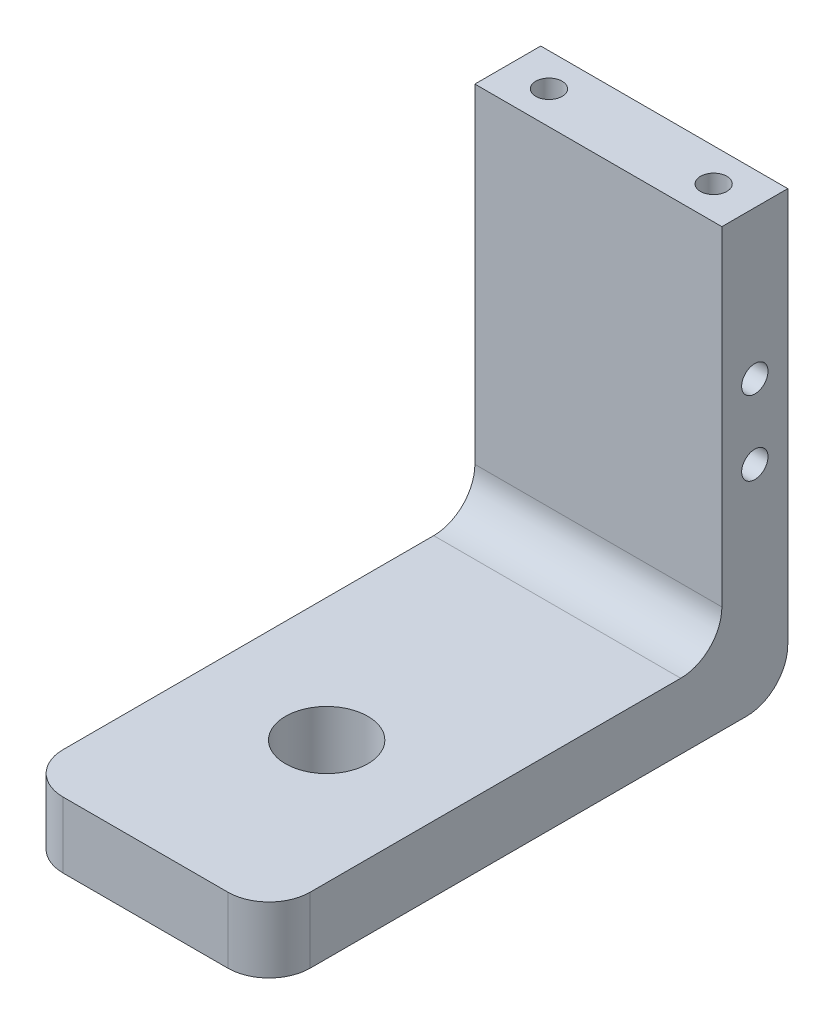
SolidWorks part; units mm, degrees
ref_plane "Front Plane" through (0, 0, 0) normal (0, 0, 1) x (1, 0, 0)
ref_plane "Top Plane" through (0, 0, 0) normal (0, 1, 0) x (1, 0, 0)
ref_plane "Right Plane" through (0, 0, 0) normal (1, 0, 0) x (0, 0, -1)
sketch "Sketch1" plane through (0, 0, 0) normal (1, 0, 0) x (0, 0, -1)
  line L1 (0, 0) -> (63, 0)
  line L2 (0, 0) -> (0, 8)
  line L3 (0, 8) -> (63, 8)
  line L4 (63, 0) -> (63, 8)
  dimension "D1" = 8
  dimension "D2" = 63
extrude "Boss-Extrude1" add sketch "Sketch1" along normal blind 30 contours L3 L4 L1 L2
sketch "Sketch2" plane through (0, 8, 0) normal (0, 1, 0) x (1, 0, 0)
  line L0 (30, 0) -> (30, 63) construction
  line L1 (0, 63) -> (30, 63)
  line L2 (0, 63) -> (0, 55)
  line L3 (0, 55) -> (30, 55)
  line L4 (30, 63) -> (30, 55)
  dimension "D1" = 8
extrude "Boss-Extrude2" add sketch "Sketch2" along normal blind 45
sketch "Sketch3" plane through (0, 8, 0) normal (0, 1, 0) x (1, 0, 0)
  line L0 (30, 0) -> (0, 0) construction
  circle A0 centre (15, 22) radius 5
  point P4 (15, 0)
  point P5 (0, 0)
  dimension "D2" = 10
  dimension "D1" = 22
extrude "Cut-Extrude1" cut sketch "Sketch3" against normal through all
sketch "Sketch4" plane through (30, 0, 0) normal (1, 0, 0) x (0, 0, -1)
  line L0 (0, 0) -> (63, 0) construction
  line L1 (55, 53) -> (63, 53) construction
  circle A0 centre (59, 35) radius 1.6
  circle A1 centre (59, 26) radius 1.6
  point P4 (0, 0)
  point P8 (59, 53)
  dimension "D1" = 3.2
  dimension "D2" = 9
  dimension "D3" = 26
extrude "Cut-Extrude2" cut sketch "Sketch4" against normal through all
sketch "Sketch5" plane through (0, 53, 0) normal (0, 1, 0) x (1, 0, 0)
  line L0 (0, 63) -> (0, 55) construction
  line L1 (30, 55) -> (30, 63) construction
  circle A0 centre (5, 59) radius 1.6
  circle A1 centre (25, 59) radius 1.6
  point P4 (0, 0)
  point P5 (0, 59)
  dimension "D1" = 3.2
  dimension "D3" = 5
  dimension "D2" = 5
extrude "Cut-Extrude3" cut sketch "Sketch5" against normal blind 14
fillet "Fillet1" radius 5 4 edges at (15, 0, -63) (15, 8, -55) (30, 4, 0) (0, 4, 0)
